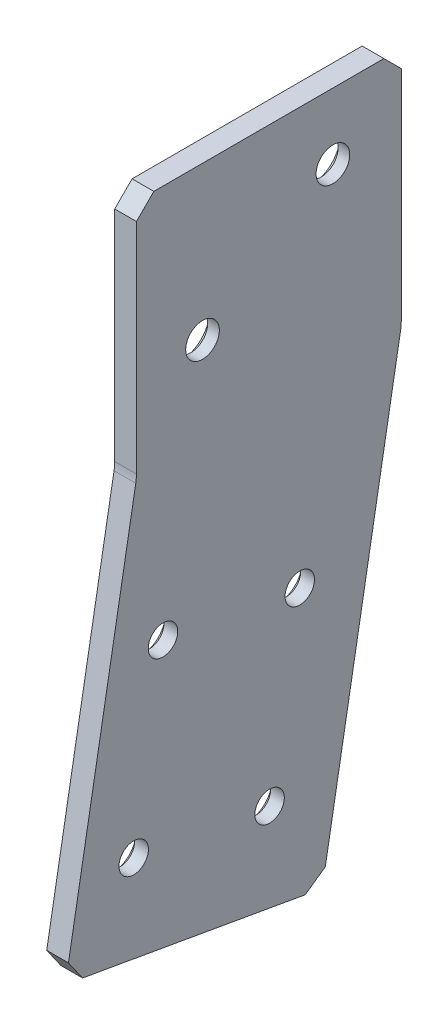
SolidWorks part; units mm, degrees
material "6061-T6 (SS)"
ref_plane "Front Plane" through (0, 0, 0) normal (0, 0, 1) x (1, 0, 0)
ref_plane "Top Plane" through (0, 0, 0) normal (0, 1, 0) x (1, 0, 0)
ref_plane "Right Plane" through (0, 0, 0) normal (1, 0, 0) x (0, 0, -1)
sketch "Sketch1" plane through (5.0358, 0, 0) normal (-1, 0, 0) x (0, 0, 1)
  line L0 (-147.7756, 230.0705) -> (-159.3146, 295.5112)
  line L1 (-159.3146, 295.5112) -> (-159.3146, 330.5632)
  line L2 (-159.3146, 330.5632) -> (-120.6268, 330.5632)
  line L3 (-120.6268, 330.5632) -> (-120.6268, 295.5112)
  line L4 (-147.7756, 230.0705) -> (-110.2544, 236.6865)
  line L5 (-139.5479, 183.4086) -> (-158.6812, 291.9191) construction
  line L6 (-110.2544, 236.6865) -> (-120.6268, 295.5112)
  line L7 (-72.8031, 24.2892) -> (-117.5036, 277.7986) construction
  line L8 (-126.9768, 330.5632) -> (-152.9646, 330.5632) construction
  circle A0 centre (-140.0751, 244.3242) radius 2.1527 construction
  dimension "D3" = 12.7
  dimension "D1" = 0
  dimension "D2" = 0
extrude "Boss-Extrude1" add sketch "Sketch1" along normal blind 3.175
fillet "Fillet1" radius 6.35 2 edges at (3.4483, 295.5112, -120.6268) (3.4483, 295.5112, -159.3146)
hole_wizard "CSK for #6 Flat Head Machine Screw (100)1" positions "Sketch3" profile "Sketch2" countersink size "#6" standard "ANSI Inch" end condition through all
sketch "Sketch3" plane through (1.8608, 0, 0) normal (-1, 0, 0) x (0, 0, 1)
  point P0 (-124.5041, 273.1394)
  point P3 (-144.4852, 269.7242)
  point P6 (-140.0751, 244.3242)
  point P9 (-120.2274, 247.7166)
sketch "Sketch2" plane through (1.8608, 273.1394, -124.5041) normal (0, 1, 0) x (0, 0, 1)
  line L0 (0, 0) -> (0, 3.175)
  line L1 (0, 3.175) -> (2.1526, 3.175)
  line L2 (2.1526, 3.175) -> (2.1526, 1.1669)
  line L3 (2.1526, 1.1669) -> (3.5433, 0)
  line L5 (3.5433, 0) -> (0, 0)
  line L6 (-2.1526, 1.1669) -> (-3.5433, 0) construction
  line L11 (0, -6.35) -> (0, 107.95) construction
  dimension "Thru Hole Dia." = 4.3053
  dimension "Thru Hole Depth" = 3.175
  dimension "Near C'Sink Dia." = 7.0866
  dimension "Near C'Sink Angle" = 100
hole_wizard "CSK for #8 Flat Head Machine Screw (100)1" positions "Sketch4" profile "Sketch5" countersink size "#8" standard "ANSI Inch" end condition through all
sketch "Sketch4" plane through (1.8608, 0, 0) normal (-1, 0, 0) x (0, 0, 1)
  point P0 (-149.3288, 320.9112)
  point P2 (-130.2788, 308.2112)
sketch "Sketch5" plane through (1.8608, 320.9112, -149.3288) normal (0, 1, 0) x (0, 0, 1)
  line L0 (0, 0) -> (0, 3.175)
  line L1 (0, 3.175) -> (2.4574, 3.175)
  line L2 (2.4574, 3.175) -> (2.4574, 1.4759)
  line L3 (2.4574, 1.4759) -> (4.2164, 0)
  line L5 (4.2164, 0) -> (0, 0)
  line L6 (-2.4574, 1.4759) -> (-4.2164, 0) construction
  line L11 (0, -6.35) -> (0, 107.95) construction
  dimension "Thru Hole Dia." = 4.9149
  dimension "Thru Hole Depth" = 3.175
  dimension "Near C'Sink Dia." = 8.4328
  dimension "Near C'Sink Angle" = 100
chamfer "Chamfer1" distance 2.54 angle 45 4 edges at (3.4483, 236.6865, -110.2544) (3.4483, 230.0705, -147.7756) (3.4483, 330.5632, -159.3146) (3.4483, 330.5632, -120.6268)
